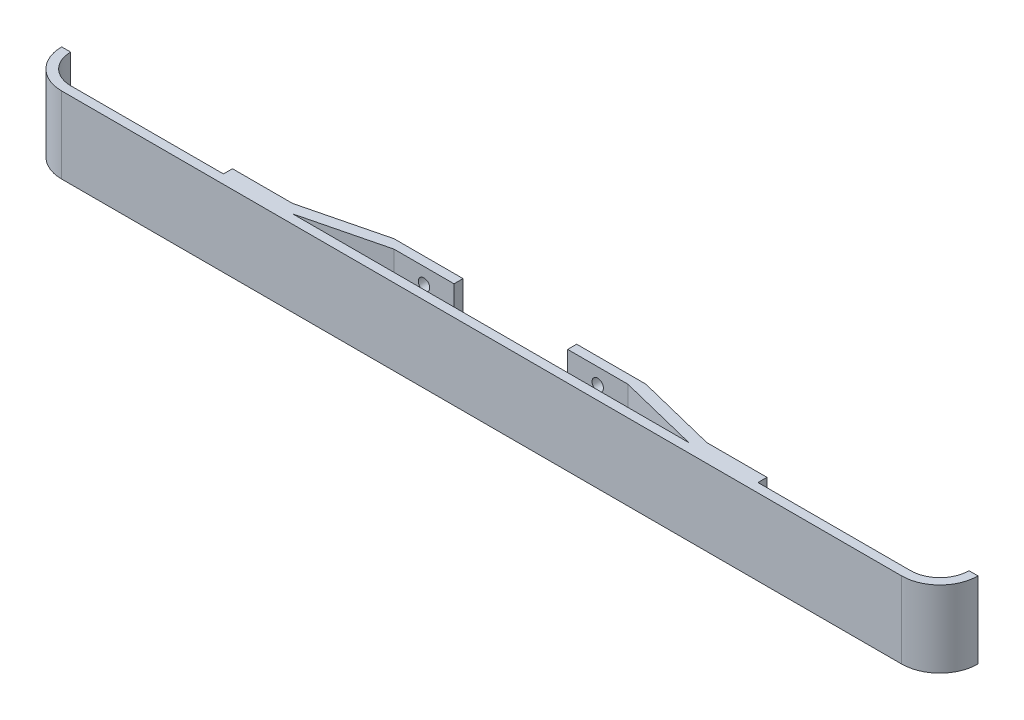
SolidWorks part; units mm, degrees
material "ABS"
ref_plane "Front Plane" through (0, 0, 0) normal (0, 0, 1) x (1, 0, 0)
ref_plane "Top Plane" through (0, 0, 0) normal (0, 1, 0) x (1, 0, 0)
ref_plane "Right Plane" through (0, 0, 0) normal (1, 0, 0) x (0, 0, -1)
sketch "Sketch1" plane through (0, 0, 0) normal (0, 0, 1) x (1, 0, 0)
  line L1 (-26.033, 10.5636) -> (278.767, 10.5636)
  line L2 (-26.033, 10.5636) -> (-26.033, -14.8364)
  line L3 (-26.033, -14.8364) -> (278.767, -14.8364)
  line L4 (278.767, 10.5636) -> (278.767, -14.8364)
  dimension "D1" = 25.4
  dimension "D2" = 304.8
extrude "Boss-Extrude2" add sketch "Sketch1" along normal blind 12.7 contours L1 L4 L3 L2
fillet "Fillet1" radius 12.7 2 edges at (-26.033, -2.1364, 12.7) (278.767, -2.1364, 12.7)
sketch "Sketch6" plane through (0, 10.5636, 0) normal (0, 1, 0) x (1, 0, 0)
  line L5 (-23.033, 0) -> (275.767, 0)
  line L6 (-13.333, -9.7) -> (266.067, -9.7)
  line L7 (-13.333, -9.7) -> (266.067, -9.7)
  arc A8 (266.067, -9.7) -> (275.767, 0) centre (266.067, 0) ccw
  arc A9 (-23.033, 0) -> (-13.333, -9.7) centre (-13.333, 0) ccw
  arc A10 (266.067, -9.7) -> (275.767, 0) centre (266.067, 0) ccw
  arc A11 (-23.033, 0) -> (-13.333, -9.7) centre (-13.333, 0) ccw
  dimension "D1" = 3
extrude "Cut-Extrude3" cut sketch "Sketch6" against normal through all
sketch "Sketch8" plane through (0, 0, 9.7) normal (0, 0, -1) x (-1, 0, 0)
  line L0 (13.333, 10.5636) -> (-266.067, 10.5636) construction
  line L1 (-145.267, 10.5636) -> (-215.267, 10.5636)
  line L2 (-145.267, 10.5636) -> (-145.267, -14.8364)
  line L3 (-145.267, -14.8364) -> (-215.267, -14.8364)
  line L4 (-215.267, 10.5636) -> (-215.267, -14.8364)
  line L5 (13.333, -14.8364) -> (-266.067, -14.8364) construction
  line L6 (-266.067, -14.8364) -> (-266.067, 10.5636) construction
  line L7 (-37.467, 10.5636) -> (-107.467, 10.5636)
  line L8 (-37.467, 10.5636) -> (-37.467, -14.8364)
  line L9 (-37.467, -14.8364) -> (-107.467, -14.8364)
  line L10 (-107.467, 10.5636) -> (-107.467, -14.8364)
  line L11 (13.333, -14.8364) -> (13.333, 10.5636) construction
  dimension "D1" = 50.8
  dimension "D2" = 70
  dimension "D3" = 50.8
  dimension "D4" = 70
extrude "Boss-Extrude3" add sketch "Sketch8" along normal blind 9.7
sketch "Sketch9" plane through (0, 10.5636, 0) normal (0, 1, 0) x (1, 0, 0)
  line L0 (145.267, -9.7) -> (165.267, -9.7)
  line L1 (165.267, -9.7) -> (192.267, -9.7)
  line L2 (192.267, -9.7) -> (165.267, -3)
  line L3 (165.267, -3) -> (145.267, -3)
  line L4 (145.267, 0) -> (145.267, -9.7) construction
  line L5 (145.267, -3) -> (145.267, -9.7)
  line L6 (145.267, 0) -> (215.267, 0) construction
  line L7 (215.267, -6.7) -> (195.267, -6.7)
  line L8 (215.267, 0) -> (215.267, -9.7) construction
  line L9 (195.267, -6.7) -> (168.267, 0)
  line L10 (168.267, 0) -> (215.267, 0)
  line L11 (215.267, 0) -> (215.267, -6.7)
  dimension "D1" = 3
  dimension "D2" = 20
  dimension "D3" = 27
  dimension "D4" = 20
  dimension "D5" = 20
  dimension "D6" = 3
  dimension "D7" = 47
extrude "Cut-Extrude4" cut sketch "Sketch9" against normal through all
sketch "Sketch12" plane through (0, 10.5636, 0) normal (0, 1, 0) x (1, 0, 0)
  line L0 (107.467, -9.7) -> (107.467, -3)
  line L1 (107.467, 0) -> (107.467, -9.7) construction
  line L2 (107.467, -3) -> (87.467, -3)
  line L3 (87.467, -3) -> (60.467, -9.7)
  line L4 (60.467, -9.7) -> (107.467, -9.7)
  line L11 (37.467, -6.7) -> (57.467, -6.7)
  line L12 (37.467, 0) -> (37.467, -9.7) construction
  line L13 (57.467, -6.7) -> (84.467, 0)
  line L14 (37.467, 0) -> (107.467, 0) construction
  line L15 (84.467, 0) -> (37.467, 0)
  line L16 (37.467, 0) -> (37.467, -6.7)
  dimension "D1" = 3
  dimension "D2" = 20
  dimension "D3" = 47
  dimension "D4" = 3
  dimension "D5" = 20
  dimension "D6" = 47
extrude "Cut-Extrude5" cut sketch "Sketch12" against normal through all
hole_wizard "#6 Clearance Hole1" positions "Sketch14" profile "Sketch15" hole size "#6" standard "ANSI Inch" end condition up to next
sketch "Sketch14" plane through (0, 0, 3) normal (0, 0, 1) x (1, 0, 0)
  line L1 (107.467, 10.5636) -> (87.467, 10.5636) construction
  line L2 (107.467, -14.8364) -> (107.467, 10.5636) construction
  point P0 (97.467, 5.3636)
  point P17 (155.267, 5.3636)
  point P18 (155.267, -9.6364)
  point P19 (97.467, -9.6364)
  dimension "D1" = 5.2
  dimension "D2" = 10
  dimension "D3" = 2
sketch "Sketch15" plane through (97.467, 5.3636, 3) normal (1, 0, 0) x (0, -1, 0)
  line L0 (0, 0) -> (0, 3)
  line L1 (0, 3) -> (1.8986, 3)
  line L2 (1.8986, 3) -> (1.8986, 0)
  line L5 (1.8986, 0) -> (0, 0)
  line L11 (0, -6.35) -> (0, 107.95) construction
  dimension "Thru Hole Dia." = 3.7973
  dimension "Thru Hole Depth" = 3
